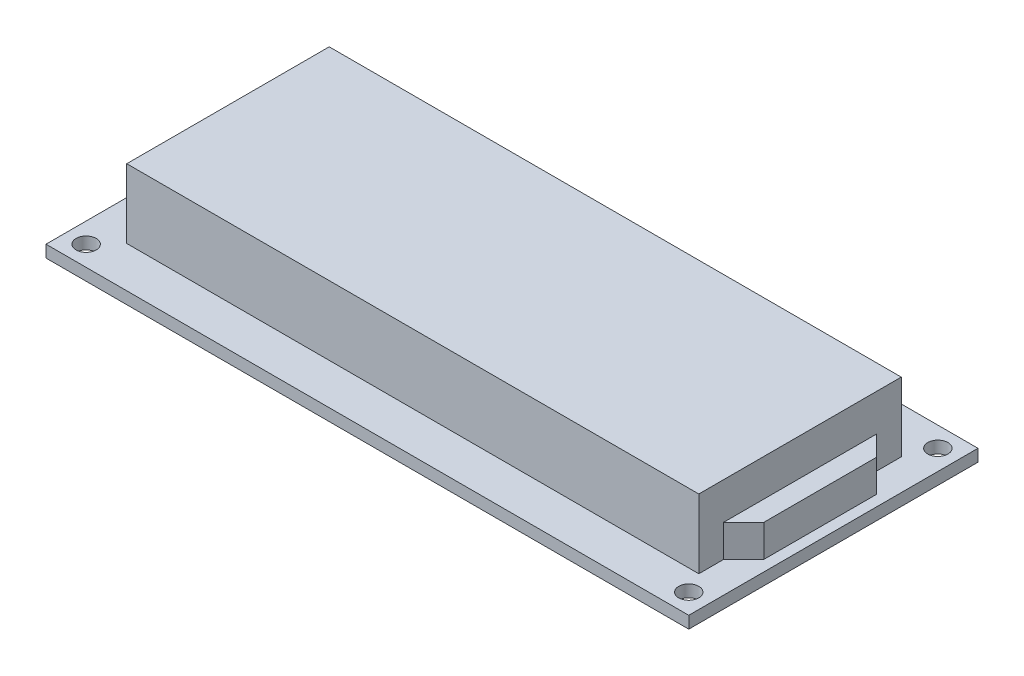
SolidWorks part; units mm, degrees
ref_plane "Piano frontale" through (0, 0, 0) normal (0, 0, 1) x (1, 0, 0)
ref_plane "Piano superiore" through (0, 0, 0) normal (0, 1, 0) x (1, 0, 0)
ref_plane "Piano destro" through (0, 0, 0) normal (1, 0, 0) x (0, 0, -1)
sketch "Schizzo1" plane through (0, 0, 0) normal (0, 1, 0) x (1, 0, 0)
  line L1 (40, -18) -> (-40, -18)
  line L2 (40, -18) -> (40, 18)
  line L3 (40, 18) -> (-40, 18)
  line L4 (-40, -18) -> (-40, 18)
  line L5 (40, -18) -> (-40, 18) construction
  line L6 (40, 18) -> (-40, -18) construction
  point P0 (0, 0)
  dimension "D1" = 36
  dimension "D2" = 80
extrude "Estrusione-Estrusione1" add sketch "Schizzo1" along normal blind 1.5
sketch "Schizzo2" plane through (0, 1.5, 0) normal (0, 1, 0) x (1, 0, 0)
  line L0 (-40, 18) -> (-40, -18) construction
  line L1 (40, 18) -> (-40, 18) construction
  line L2 (-37.5, 15.5) -> (40, 15.5) construction
  line L3 (40, -18) -> (40, 18) construction
  line L4 (37.5, 15.5) -> (37.5, -18) construction
  line L5 (-40, -18) -> (40, -18) construction
  line L6 (-37.5, 15.5) -> (-37.5, -18) construction
  circle A0 centre (-37.5, 15.5) radius 1.25
  circle A1 centre (37.5, 15.5) radius 1.25
  circle A2 centre (-37.5, -15.5) radius 1.25
  circle A3 centre (37.5, -15.5) radius 1.25
  dimension "D1" = 2.5
  dimension "D4" = 2.5
  dimension "D6" = 2.5
  dimension "D7" = 2.5
  dimension "D2" = 2.5
  dimension "D3" = 2.5
  dimension "D5" = 2.5
  dimension "D8" = 2.5
  dimension "D9" = 2.5
extrude "Taglio-Estrusione1" cut sketch "Schizzo2" against normal blind 1.5
sketch "Schizzo3" plane through (0, 1.5, 0) normal (0, 1, 0) x (1, 0, 0)
  line L0 (-40, 18) -> (-40, -18) construction
  line L1 (-35.05, 12.3) -> (36.15, 12.3)
  line L2 (-35.05, 12.3) -> (-35.05, -12.9)
  line L3 (-35.05, -12.9) -> (36.15, -12.9)
  line L4 (36.15, 12.3) -> (36.15, -12.9)
  line L5 (40, 18) -> (-40, 18) construction
  line L6 (-35.05, -0.3) -> (42.028, -0.3) construction
  line L7 (38.65, -0.3) -> (38.65, 6.7)
  line L8 (38.65, 6.7) -> (38.65, -7.3)
  line L9 (36.15, -0.3) -> (36.15, -9.8)
  line L10 (36.15, -0.3) -> (36.15, 9.2)
  line L11 (36.15, 9.2) -> (38.65, 6.7)
  line L12 (36.15, -9.8) -> (38.65, -7.3)
  dimension "D1" = 25.2
  dimension "D2" = 71.2
  dimension "D3" = 4.95
  dimension "D4" = 5.7
  dimension "D5" = 2.5
  dimension "D6" = 7
  dimension "D7" = 7
  dimension "D8" = 9.5
  dimension "D9" = 9.5
extrude "Estrusione-Estrusione2" add sketch "Schizzo3" along normal blind 8.6 contours L2 L6 L4 L1 | L6 L2 L3 L4 region at (0.55, 1.5, -6) region at (0.55, 1.5, 6.6)
extrude "Estrusione-Estrusione3" add sketch "Schizzo3<3>" along normal blind 4 contours L6 L4 L12 L8 | L4 L6 L7 L11 region at (37.3369, 1.5, -3.8566) region at (37.3369, 1.5, 4.4566)
sketch "Schizzo3<3>" plane through (0, 1.5, 0) normal (0, 1, 0) x (1, 0, 0) same geometry as "Schizzo3"
sketch "Schizzo4" plane through (0, 0, 0) normal (0, -1, 0) x (1, 0, 0)
  line L0 (40, -18) -> (-40, -18) construction
  line L1 (-33, -17.5) -> (8, -17.5)
  line L2 (-33, -17.5) -> (-33, -14.96)
  line L3 (-33, -14.96) -> (8, -14.96)
  line L4 (8, -17.5) -> (8, -14.96)
  line L5 (-40, -18) -> (-40, 18) construction
  dimension "D1" = 2.54
  dimension "D2" = 0.5
  dimension "D3" = 41
  dimension "D4" = 7
extrude "Estrusione-Estrusione4" add sketch "Schizzo4" along normal blind 18
